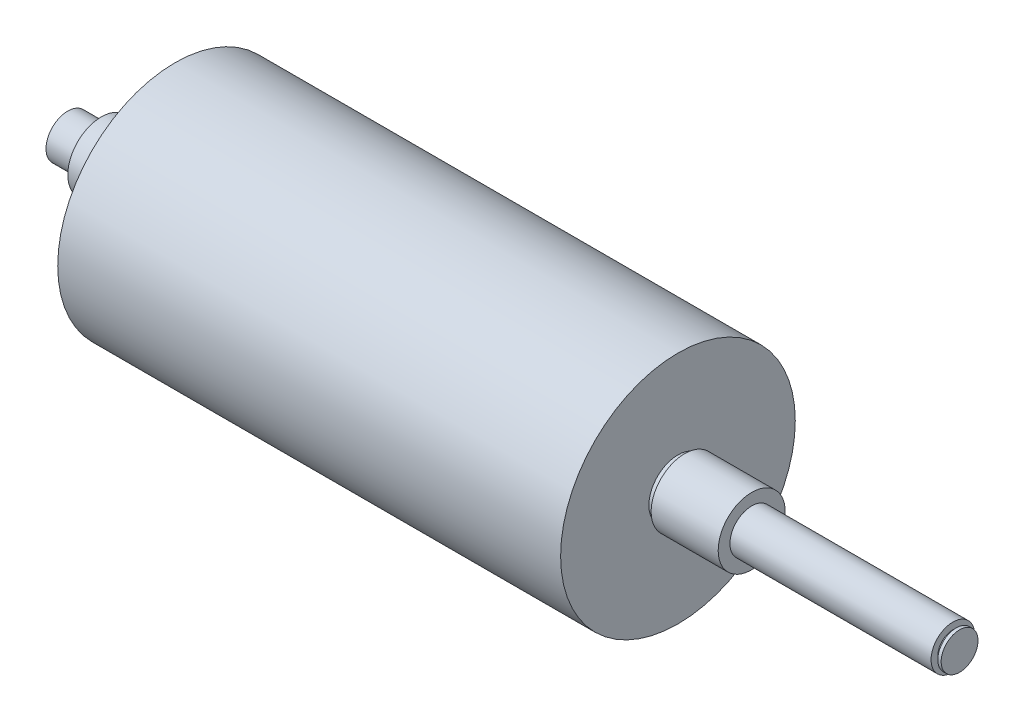
SolidWorks part; units mm, degrees
ref_plane "Plan de face" through (0, 0, 0) normal (0, 0, 1) x (1, 0, 0)
ref_plane "Plan de dessus" through (0, 0, 0) normal (0, 1, 0) x (1, 0, 0)
ref_plane "Plan de droite" through (0, 0, 0) normal (1, 0, 0) x (0, 0, -1)
sketch "Esquisse1" plane through (0, 0, 0) normal (0, 0, 1) x (1, 0, 0)
  line L0 (0, 0) -> (0, 100)
  line L1 (0, 100) -> (300, 100)
  line L2 (300, 100) -> (300, 74.3143)
  line L3 (300, 74.3143) -> (320, 74.3143)
  line L4 (320, 74.3143) -> (320, 350)
  line L5 (320, 350) -> (1820, 350)
  line L6 (1820, 350) -> (1820, 86.7213)
  line L7 (1820, 86.7213) -> (1840, 86.7213)
  line L8 (1840, 86.7213) -> (1840, 100)
  line L9 (1840, 100) -> (2140, 100)
  line L10 (2140, 100) -> (2140, 0)
  line L11 (2140, 0) -> (0, 0)
  dimension "D1" = 1500
  dimension "D2" = 300
  dimension "D3" = 20
  dimension "D4" = 20
  dimension "D5" = 300
  dimension "D6" = 350
  dimension "D7" = 100
  dimension "D8" = 100
revolve "Révolution1" add sketch "Esquisse1" angle 360 about L11 region at (1070.3206, 161.5132, 0)
sketch "Esquisse2" plane through (0, 0, 0) normal (-1, 0, 0) x (0, 0, 1)
  circle A0 centre (0, 0) radius 65
  circle A1 centre (0, 0) radius 100 construction
  circle A2 centre (0, 0) radius 100
  dimension "D1" = 130
extrude "Enlèv. mat.-Extru.1" cut sketch "Esquisse2" against normal blind 100
sketch "Esquisse3" plane through (2140, 0, 0) normal (1, 0, 0) x (0, 0, -1)
  circle A0 centre (0, 0) radius 65
  circle A1 centre (0, 0) radius 100 construction
  circle A2 centre (0, 0) radius 100
extrude "Enlèv. mat.-Extru.2" cut sketch "Esquisse3" against normal blind 100
sketch "Esquisse5" plane through (2140, 0, 0) normal (1, 0, 0) x (0, 0, -1)
  circle A1 centre (0, 0) radius 65
  circle A2 centre (0, 0) radius 65
  dimension "D1" = 0
extrude "Boss.-Extru.2" add sketch "Esquisse5" along normal blind 520
sketch "Esquisse6" plane through (2660, 0, 0) normal (1, 0, 0) x (0, 0, -1)
  circle A0 centre (0, 0) radius 65
  circle A1 centre (0, 0) radius 45
extrude "Enlèv. mat.-Extru.3" cut sketch "Esquisse6" against normal blind 20
sketch "Esquisse7" plane through (2660, 0, 0) normal (1, 0, 0) x (0, 0, -1)
  circle A0 centre (0, 0) radius 55
extrude "Boss.-Extru.3" add sketch "Esquisse7" against normal blind 10
